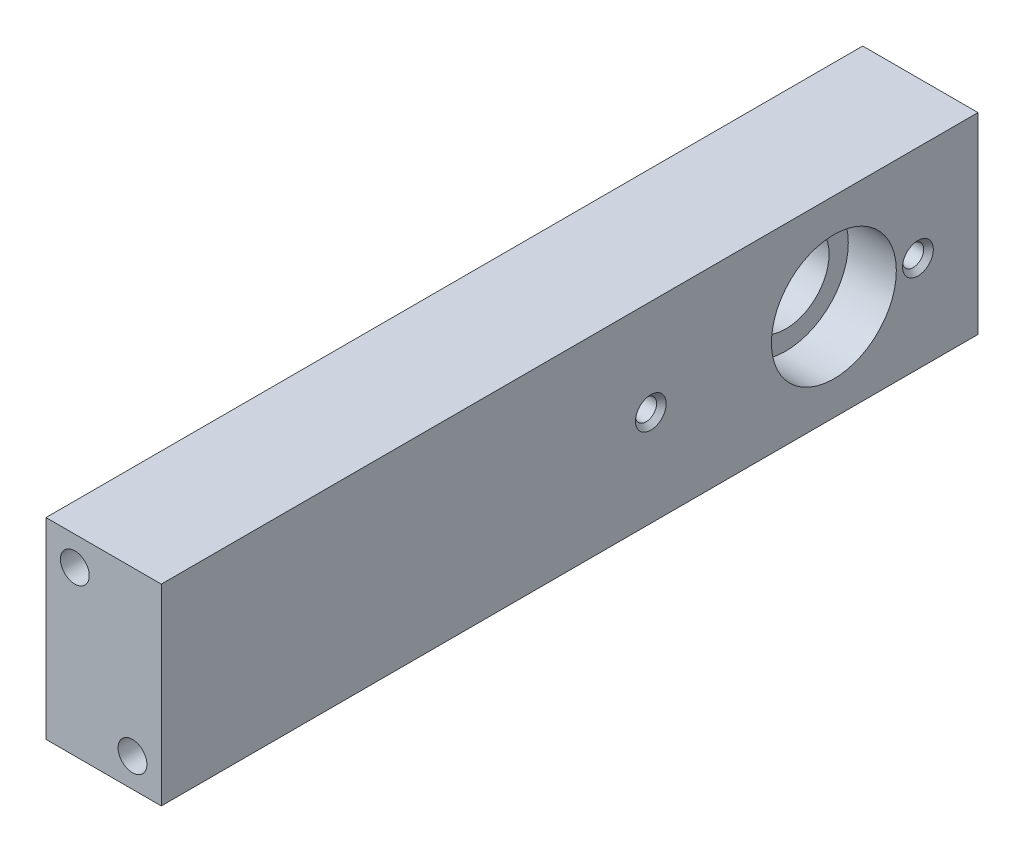
SolidWorks part; units mm, degrees
ref_plane "Płaszczyzna przednia" through (0, 0, 0) normal (0, 0, 1) x (1, 0, 0)
ref_plane "Płaszczyzna górna" through (0, 0, 0) normal (0, 1, 0) x (1, 0, 0)
ref_plane "Płaszczyzna prawa" through (0, 0, 0) normal (1, 0, 0) x (0, 0, -1)
sketch "Szkic1" plane through (0, 0, 0) normal (0, 0, 1) x (1, 0, 0)
  line L1 (-6, -10) -> (6, -10)
  line L2 (-6, -10) -> (-6, 10)
  line L3 (-6, 10) -> (6, 10)
  line L4 (6, -10) -> (6, 10)
  line L5 (-6, -10) -> (6, 10) construction
  line L6 (-6, 10) -> (6, -10) construction
  point P0 (0, 0)
  dimension "D1" = 20
  dimension "D2" = 12
extrude "Dodanie-wyciągnięcie1" add sketch "Szkic1" along normal blind 85
sketch "Szkic2" plane through (0, 0, 85) normal (0, 0, 1) x (1, 0, 0)
  line L0 (6, -10) -> (6, 10) construction
  line L1 (-6, -10) -> (6, -10) construction
  line L2 (-6, 10) -> (-6, -10) construction
  line L3 (6, 10) -> (-6, 10) construction
  circle A0 centre (-3, 7) radius 1.5
  circle A1 centre (3, -7) radius 1.5
  dimension "D1" = 3
  dimension "D2" = 3
  dimension "D3" = 3
  dimension "D4" = 3
  dimension "D5" = 3
  dimension "D6" = 3
extrude "Wytnij-wyciągnięcie1" cut sketch "Szkic2" against normal blind 10
sketch "Szkic4" plane through (6, 0, 0) normal (1, 0, 0) x (0, 0, -1)
  line L0 (-85, 10) -> (0, 10) construction
  line L1 (-85, -10) -> (-85, 10) construction
  circle A0 centre (-15, 0) radius 6.5
  dimension "D1" = 13
  dimension "D2" = 10
  dimension "D3" = 70
extrude "Wytnij-wyciągnięcie2" cut sketch "Szkic4" against normal blind 5
sketch "Szkic5" plane through (-6, 0, 0) normal (-1, 0, 0) x (0, 0, 1)
  line L0 (85, -10) -> (0, -10) construction
  line L1 (85, 10) -> (85, -10) construction
  circle A0 centre (15, 0) radius 4.5
  dimension "D1" = 9
  dimension "D2" = 10
  dimension "D3" = 70
extrude "Wytnij-wyciągnięcie3" cut sketch "Szkic5" against normal through all
sketch "Szkic6" plane through (-6, 0, 0) normal (-1, 0, 0) x (0, 0, 1)
  circle A0 centre (34.05, 0) radius 1.1
extrude "Wytnij-wyciągnięcie4" cut sketch "Szkic6" against normal through all
chamfer "Sfazowanie1" distance 0.5 angle 45 1 edges at (6, 0, 35.15)
sketch "Szkic7" plane through (-6, 0, 0) normal (-1, 0, 0) x (0, 0, 1)
  circle A0 centre (6.25, 0) radius 1.1
extrude "Wytnij-wyciągnięcie5" cut sketch "Szkic7" against normal through all
chamfer "Sfazowanie2" distance 0.5 angle 45 1 edges at (6, 0, 7.35)
